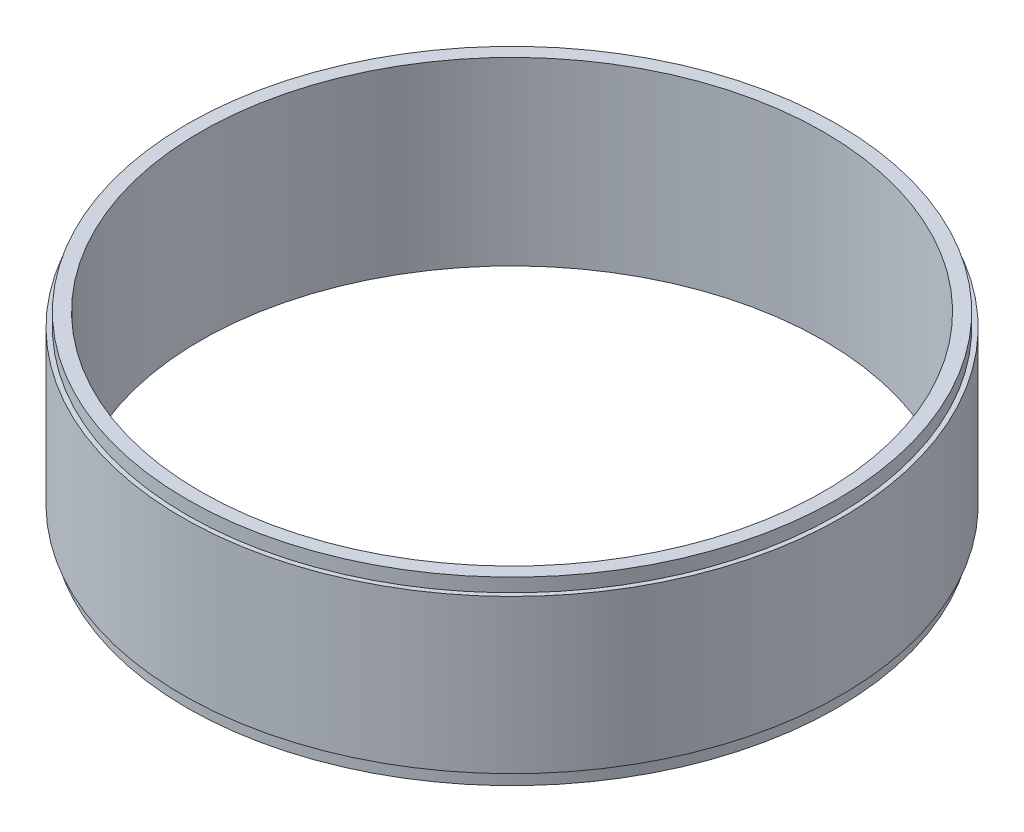
SolidWorks part; units mm, degrees
material "Silica Phenolic"
ref_plane "Piano frontale" through (0, 0, 0) normal (0, 0, 1) x (1, 0, 0)
ref_plane "Piano superiore" through (0, 0, 0) normal (0, 1, 0) x (1, 0, 0)
ref_plane "Piano destro" through (0, 0, 0) normal (1, 0, 0) x (0, 0, -1)
sketch "Schizzo1" plane through (0, 0, 0) normal (0, 0, 1) x (1, 0, 0)
  line L0 (-69, 6.8923) -> (-69, 0)
  line L3 (-72, 40) -> (-69, 40)
  line L8 (0, 0) -> (0, 47.1479) construction
  line L9 (-69, 0) -> (-72, 0)
  line L10 (-72, 0) -> (-72, 3)
  line L11 (-72, 3) -> (-73, 3)
  line L12 (-69, 6.8923) -> (-69, 40)
  line L13 (-73, 3) -> (-73, 37)
  line L14 (-73, 37) -> (-72, 37)
  line L15 (-72, 37) -> (-72, 40)
  point P2 (-71, 6.8923)
  point P11 (0, 0)
  dimension "D1" = 1
  dimension "D2" = 3
  dimension "D3" = 3
  dimension "D4" = 1
  dimension "D5" = 3
  dimension "D6" = 40
  dimension "D7" = 146
revolve "Rivoluzione1" add sketch "Schizzo1" angle 360 about L8 region at (-70.9416, 20, 0)
